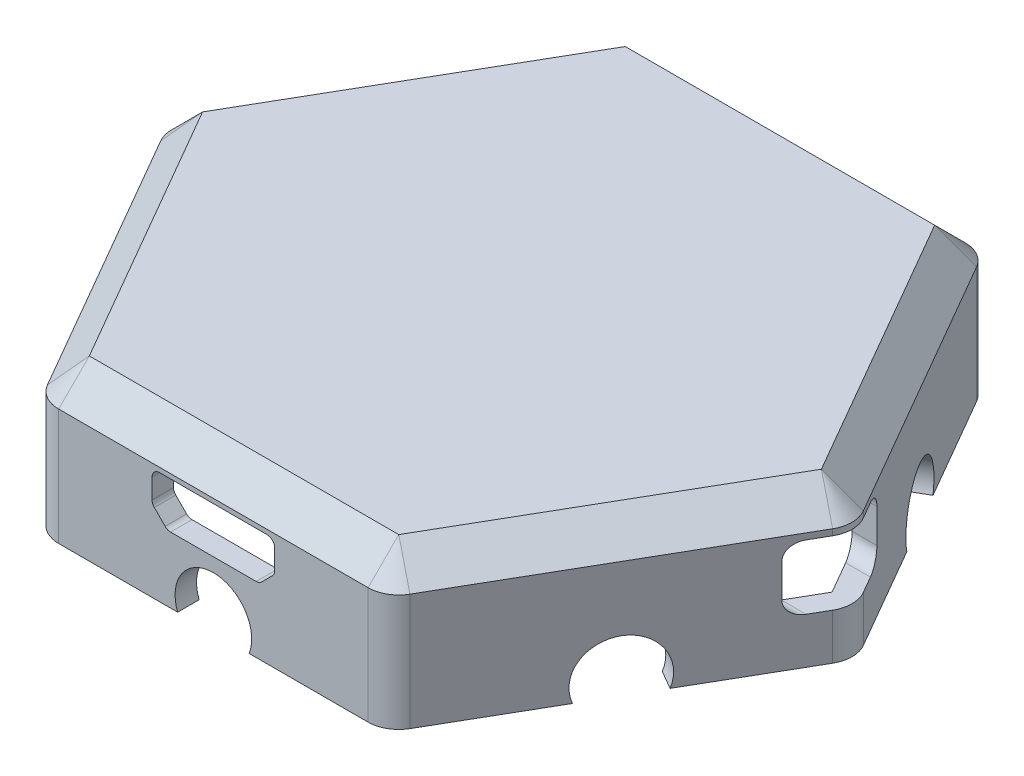
SolidWorks part; units mm, degrees
ref_plane "Front Plane" through (0, 0, 0) normal (0, 0, 1) x (1, 0, 0)
ref_plane "Top Plane" through (0, 0, 0) normal (0, 1, 0) x (1, 0, 0)
ref_plane "Right Plane" through (0, 0, 0) normal (1, 0, 0) x (0, 0, -1)
sketch "Sketch1" plane through (0, 0, 0) normal (0, 1, 0) x (1, 0, 0)
  line L0 (22.5, 0) -> (0, 0) construction
  line L1 (22.5, 0) -> (11.25, 19.4856)
  line L2 (11.25, 19.4856) -> (-11.25, 19.4856)
  line L3 (-11.25, 19.4856) -> (-22.5, 0)
  line L4 (-22.5, 0) -> (-11.25, -19.4856)
  line L5 (-11.25, -19.4856) -> (11.25, -19.4856)
  line L6 (11.25, -19.4856) -> (22.5, 0)
  circle A0 centre (0, 0) radius 19.4856 construction
  dimension "D1" = 22.5
extrude "Boss-Extrude1" add sketch "Sketch1" along normal blind 5
sketch "Sketch2" plane through (0, 0, 0) normal (0, -1, 0) x (1, 0, 0)
  line L0 (-10.4417, 18.0856) -> (-20.8834, 0)
  line L1 (-20.8834, 0) -> (-10.4417, -18.0856)
  line L2 (-10.4417, -18.0856) -> (10.4417, -18.0856)
  line L3 (10.4417, -18.0856) -> (20.8834, 0)
  line L4 (20.8834, 0) -> (10.4417, 18.0856)
  line L5 (10.4417, 18.0856) -> (-10.4417, 18.0856)
  line L6 (22.5, 0) -> (11.25, 19.4856)
  line L7 (11.25, 19.4856) -> (-11.25, 19.4856)
  line L8 (-11.25, 19.4856) -> (-22.5, 0)
  line L9 (-22.5, 0) -> (-11.25, -19.4856)
  line L10 (-11.25, -19.4856) -> (11.25, -19.4856)
  line L11 (11.25, -19.4856) -> (22.5, 0)
  line L12 (22.5, 0) -> (11.25, 19.4856)
  line L13 (11.25, 19.4856) -> (-11.25, 19.4856)
  line L14 (-11.25, 19.4856) -> (-22.5, 0)
  line L15 (-22.5, 0) -> (-11.25, -19.4856)
  line L16 (-11.25, -19.4856) -> (11.25, -19.4856)
  line L17 (11.25, -19.4856) -> (22.5, 0)
  dimension "D1" = 0
  dimension "D2" = 1.4
extrude "Cut-Extrude1" cut sketch "Sketch2" against normal blind 3.6 contours L4 L5 L0 L1 L2 L3 region at (0, 0, 0)
sketch "Sketch3" plane through (0, 0, 0) normal (0, -1, 0) x (1, 0, 0)
  line L6 (22.5, 0) -> (11.25, 19.4856)
  line L7 (11.25, 19.4856) -> (-11.25, 19.4856)
  line L8 (-11.25, 19.4856) -> (-22.5, 0)
  line L9 (-22.5, 0) -> (-11.25, -19.4856)
  line L10 (-11.25, -19.4856) -> (11.25, -19.4856)
  line L11 (11.25, -19.4856) -> (22.5, 0)
  line L12 (22.5, 0) -> (11.25, 19.4856)
  line L13 (11.25, 19.4856) -> (-11.25, 19.4856)
  line L14 (-11.25, 19.4856) -> (-22.5, 0)
  line L15 (-22.5, 0) -> (-11.25, -19.4856)
  line L16 (-11.25, -19.4856) -> (11.25, -19.4856)
  line L17 (11.25, -19.4856) -> (22.5, 0)
  line L18 (10.4417, 18.0856) -> (-10.4417, 18.0856)
  line L19 (20.8834, 0) -> (10.4417, 18.0856)
  line L20 (10.4417, -18.0856) -> (20.8834, 0)
  line L21 (-10.4417, -18.0856) -> (10.4417, -18.0856)
  line L22 (-20.8834, 0) -> (-10.4417, -18.0856)
  line L23 (-10.4417, 18.0856) -> (-20.8834, 0)
  line L24 (10.4417, 18.0856) -> (-10.4417, 18.0856)
  line L25 (20.8834, 0) -> (10.4417, 18.0856)
  line L26 (10.4417, -18.0856) -> (20.8834, 0)
  line L27 (-10.4417, -18.0856) -> (10.4417, -18.0856)
  line L28 (-20.8834, 0) -> (-10.4417, -18.0856)
  line L29 (-10.4417, 18.0856) -> (-20.8834, 0)
  dimension "D1" = 0
  dimension "D2" = 0
extrude "Boss-Extrude2" add sketch "Sketch3" along normal blind 4.6
fillet "Fillet1" radius 2 6 edges at (-11.25, 0.2, 19.4856) (-22.5, 0.2, 0) (-11.25, 0.2, -19.4856) (11.25, 0.2, -19.4856) (22.5, 0.2, 0) (11.25, 0.2, 19.4856)
sketch "Sketch4" plane through (0, 0, -19.4856) normal (0, 0, -1) x (-1, 0, 0)
  line L0 (0, -3.6) -> (0, -3.7) construction
  line L2 (0, -3.6) -> (0, 0) construction
  circle A0 centre (0, -3.7) radius 2.5
  dimension "D1" = 0.1
  dimension "D2" = 5
  dimension "D3" = 3.6
extrude "Cut-Extrude2" cut sketch "Sketch4" against normal up to next
ref_axis "Axis1" through (0, 4.51, 0) along (0, -1, 0)
pattern_circular "CirPattern1" count 6 every 60 about axis through (0, 4.51, 0) along (0, -1, 0) of "Cut-Extrude2"
sketch "Sketch5" plane through (0, 0, 19.4856) normal (0, 0, 1) x (1, 0, 0)
  line L3 (0, -0.3) -> (0, 2.7) construction
  line L4 (0, 5) -> (0, 2.7) construction
  line L5 (-10.0953, 5) -> (10.0953, 5) construction
  line L7 (-3.5, 2.7) -> (3.5, 2.7)
  line L8 (4, 2.2) -> (4, 0.9071)
  line L9 (3.8536, 0.5536) -> (3.1464, -0.1536)
  line L10 (2.7929, -0.3) -> (-2.7929, -0.3)
  line L11 (-3.8536, 0.5536) -> (-3.1464, -0.1536)
  line L12 (-4, 2.2) -> (-4, 0.9071)
  arc A4 (3.1464, -0.1536) -> (2.7929, -0.3) centre (2.7929, 0.2) cw
  arc A5 (4, 0.9071) -> (3.8536, 0.5536) centre (3.5, 0.9071) cw
  arc A6 (3.5, 2.7) -> (4, 2.2) centre (3.5, 2.2) cw
  arc A7 (-3.5, 2.7) -> (-4, 2.2) centre (-3.5, 2.2) ccw
  arc A8 (-4, 0.9071) -> (-3.8536, 0.5536) centre (-3.5, 0.9071) ccw
  arc A9 (-3.1464, -0.1536) -> (-2.7929, -0.3) centre (-2.7929, 0.2) ccw
  point P7 (3, -0.3)
  point P10 (4, 0.7)
  point P16 (4, 2.7)
  point P26 (-4, 2.7)
  point P27 (-4, 0.7)
  point P28 (-3, -0.3)
  dimension "D4" = 3
  dimension "D6" = 0.5
  dimension "D1" = 3
  dimension "D2" = 4
  dimension "D3" = 2
  dimension "D5" = 2.3
extrude "Cut-Extrude3" cut sketch "Sketch5" against normal blind 8
sketch "Sketch7" plane through (0, 0, 0) normal (1, 0, 0) x (0, 0, -1)
  line L0 (0, 0.5) -> (0, 5) construction
  line L1 (-3.1, -1.6) -> (3.1, -1.6)
  line L2 (-3.1, -1.6) -> (-3.1, 2.6)
  line L3 (-3.1, 2.6) -> (3.1, 2.6)
  line L4 (3.1, -1.6) -> (3.1, 2.6)
  line L5 (-3.1, -1.6) -> (3.1, 2.6) construction
  line L6 (-3.1, 2.6) -> (3.1, -1.6) construction
  line L7 (1, 5) -> (-1, 5) construction
  point P0 (0, 0.5)
  dimension "D1" = 4.2
  dimension "D2" = 6.2
  dimension "D3" = 4.5
extrude "Cut-Extrude4" cut sketch "Sketch7" against normal blind 10 from offset 22.5
fillet "Fillet2" radius 1 4 edges at (19.9019, -1.6, 3.1) (19.9019, -1.6, -3.1) (19.9019, 2.6, -3.1) (19.9019, 2.6, 3.1)
chamfer "Chamfer1" distance 2 angle 45 12 edges at (0, 5, 19.4856) (11.0953, 5, 19.2176) (-11.0953, 5, 19.2176) (16.875, 5, 9.7428) (-16.875, 5, 9.7428) (22.1906, 5, 0) (-22.1906, 5, 0) (16.875, 5, -9.7428) (-16.875, 5, -9.7428) (11.0953, 5, -19.2176) (-11.0953, 5, -19.2176) (0, 5, -19.4856)
chamfer "Chamfer2" distance 1 angle 45 6 edges at (15.6626, 3.6, 9.0428) (15.6626, 3.6, -9.0428) (0, 3.6, -18.0856) (0, 3.6, 18.0856) (-15.6626, 3.6, 9.0428) (-15.6626, 3.6, -9.0428)
sketch "Sketch12" plane through (0, 3.6, 0) normal (0, -1, 0) x (1, 0, 0)
  line L1 (-18.0412, -7.7229) -> (-16.8288, -7.0229) construction
  line L2 (-16.8288, -7.0229) -> (-20.8834, 0) construction
  line L3 (-20.8834, 0) -> (-16.8288, 7.0229) construction
  line L4 (-16.8288, 7.0229) -> (-18.0412, 7.7229) construction
  line L5 (-18.0412, 7.7229) -> (-21.9226, 1) construction
  line L6 (-21.9226, -1) -> (-18.0412, -7.7229) construction
  line L7 (-15.7088, 11.7627) -> (-14.4964, 11.0627)
  line L8 (-14.4964, 11.0627) -> (-10.4417, 18.0856)
  line L9 (-10.4417, 18.0856) -> (-2.3324, 18.0856)
  line L17 (19.7287, 0) -> (9.8644, 17.0856)
  line L18 (19.7287, 0) -> (9.8644, 17.0856)
  line L19 (9.8644, 17.0856) -> (-9.8644, 17.0856)
  line L30 (-2.3324, 18.0856) -> (-2.3324, 19.4856)
  line L31 (-2.3324, 19.4856) -> (-10.0953, 19.4856)
  line L32 (-11.8274, 18.4856) -> (-15.7088, 11.7627)
  line L33 (-15.7088, 11.7627) -> (-14.4964, 11.0627)
  line L34 (-14.4964, 11.0627) -> (-10.4417, 18.0856)
  line L35 (-10.4417, 18.0856) -> (-2.3324, 18.0856)
  line L36 (-2.3324, 18.0856) -> (-2.3324, 19.4856)
  line L37 (-2.3324, 19.4856) -> (-10.0953, 19.4856)
  line L38 (-11.8274, 18.4856) -> (-15.7088, 11.7627)
  line L39 (-14.4964, -11.0627) -> (-15.7088, -11.7627) construction
  line L40 (-15.7088, -11.7627) -> (-11.8274, -18.4856) construction
  line L41 (-10.0953, -19.4856) -> (-2.3324, -19.4856) construction
  line L42 (-2.3324, -19.4856) -> (-2.3324, -18.0856) construction
  line L43 (-2.3324, -18.0856) -> (-10.4417, -18.0856) construction
  line L44 (-10.4417, -18.0856) -> (-14.4964, -11.0627) construction
  line L45 (15.7088, -11.7627) -> (14.4964, -11.0627) construction
  line L46 (14.4964, -11.0627) -> (10.4417, -18.0856) construction
  line L47 (10.4417, -18.0856) -> (2.3324, -18.0856) construction
  line L48 (2.3324, -18.0856) -> (2.3324, -19.4856) construction
  line L49 (2.3324, -19.4856) -> (10.0953, -19.4856) construction
  line L50 (11.8274, -18.4856) -> (15.7088, -11.7627) construction
  line L51 (18.0412, 7.7229) -> (16.8288, 7.0229) construction
  line L52 (16.8288, 7.0229) -> (20.8834, 0) construction
  line L53 (20.8834, 0) -> (16.8288, -7.0229) construction
  line L54 (16.8288, -7.0229) -> (18.0412, -7.7229) construction
  line L55 (18.0412, -7.7229) -> (21.9226, -1) construction
  line L56 (21.9226, 1) -> (18.0412, 7.7229) construction
  line L57 (2.3324, 19.4856) -> (2.3324, 18.0856) construction
  line L58 (2.3324, 18.0856) -> (10.4417, 18.0856) construction
  line L59 (10.4417, 18.0856) -> (14.4964, 11.0627) construction
  line L60 (14.4964, 11.0627) -> (15.7088, 11.7627) construction
  line L61 (15.7088, 11.7627) -> (11.8274, 18.4856) construction
  line L62 (10.0953, 19.4856) -> (2.3324, 19.4856) construction
  line L63 (-18.0412, -7.7229) -> (-16.8288, -7.0229)
  line L64 (-16.8288, -7.0229) -> (-20.8834, 0)
  line L65 (-20.8834, 0) -> (-16.8288, 7.0229)
  line L66 (-16.8288, 7.0229) -> (-18.0412, 7.7229)
  line L67 (-18.0412, 7.7229) -> (-21.9226, 1)
  line L68 (-21.9226, -1) -> (-18.0412, -7.7229)
  line L69 (-14.4964, -11.0627) -> (-15.7088, -11.7627)
  line L70 (-15.7088, -11.7627) -> (-11.8274, -18.4856)
  line L71 (-10.0953, -19.4856) -> (-2.3324, -19.4856)
  line L72 (-2.3324, -19.4856) -> (-2.3324, -18.0856)
  line L73 (-2.3324, -18.0856) -> (-10.4417, -18.0856)
  line L74 (-10.4417, -18.0856) -> (-14.4964, -11.0627)
  line L75 (15.7088, -11.7627) -> (14.4964, -11.0627)
  line L76 (14.4964, -11.0627) -> (10.4417, -18.0856)
  line L77 (10.4417, -18.0856) -> (2.3324, -18.0856)
  line L78 (2.3324, -18.0856) -> (2.3324, -19.4856)
  line L79 (2.3324, -19.4856) -> (10.0953, -19.4856)
  line L80 (11.8274, -18.4856) -> (15.7088, -11.7627)
  line L81 (18.0412, 7.7229) -> (16.8288, 7.0229)
  line L82 (16.8288, 7.0229) -> (20.8834, 0)
  line L83 (20.8834, 0) -> (16.8288, -7.0229)
  line L84 (16.8288, -7.0229) -> (18.0412, -7.7229)
  line L85 (18.0412, -7.7229) -> (21.9226, -1)
  line L86 (21.9226, 1) -> (18.0412, 7.7229)
  line L87 (2.3324, 19.4856) -> (2.3324, 18.0856)
  line L88 (2.3324, 18.0856) -> (10.4417, 18.0856)
  line L89 (10.4417, 18.0856) -> (14.4964, 11.0627)
  line L90 (14.4964, 11.0627) -> (15.7088, 11.7627)
  line L91 (15.7088, 11.7627) -> (11.8274, 18.4856)
  line L92 (10.0953, 19.4856) -> (2.3324, 19.4856)
  line L105 (9.8644, 17.0856) -> (-9.8644, 17.0856)
  line L116 (-9.8644, 17.0856) -> (-19.7287, 0)
  line L117 (-9.8644, 17.0856) -> (-19.7287, 0)
  line L118 (-19.7287, 0) -> (-9.8644, -17.0856)
  line L119 (-19.7287, 0) -> (-9.8644, -17.0856)
  line L120 (-9.8644, -17.0856) -> (9.8644, -17.0856)
  line L121 (-9.8644, -17.0856) -> (9.8644, -17.0856)
  line L122 (9.8644, -17.0856) -> (19.7287, 0)
  line L123 (9.8644, -17.0856) -> (19.7287, 0)
  arc A0 (8.4417, 18.0856) -> (11.4417, 16.3535) centre (10.4417, 18.0856) ccw
  arc A1 (-21.9226, 1) -> (-21.9226, -1) centre (-20.1906, 0) ccw construction
  arc A2 (-10.0953, 19.4856) -> (-11.8274, 18.4856) centre (-10.0953, 17.4856) ccw
  arc A3 (-10.0953, 19.4856) -> (-11.8274, 18.4856) centre (-10.0953, 17.4856) ccw
  arc A4 (-11.8274, -18.4856) -> (-10.0953, -19.4856) centre (-10.0953, -17.4856) ccw construction
  arc A5 (10.0953, -19.4856) -> (11.8274, -18.4856) centre (10.0953, -17.4856) ccw construction
  arc A6 (21.9226, -1) -> (21.9226, 1) centre (20.1906, 0) ccw construction
  arc A7 (11.8274, 18.4856) -> (10.0953, 19.4856) centre (10.0953, 17.4856) ccw construction
  arc A8 (-21.9226, 1) -> (-21.9226, -1) centre (-20.1906, 0) ccw
  arc A9 (-11.8274, -18.4856) -> (-10.0953, -19.4856) centre (-10.0953, -17.4856) ccw
  arc A10 (10.0953, -19.4856) -> (11.8274, -18.4856) centre (10.0953, -17.4856) ccw
  arc A11 (21.9226, -1) -> (21.9226, 1) centre (20.1906, 0) ccw
  arc A12 (11.8274, 18.4856) -> (10.0953, 19.4856) centre (10.0953, 17.4856) ccw
  arc A13 (11.4417, -16.3535) -> (8.4417, -18.0856) centre (10.4417, -18.0856) ccw
  arc A14 (-8.4417, -18.0856) -> (-11.4417, -16.3535) centre (-10.4417, -18.0856) ccw
  arc A15 (-11.4417, 16.3535) -> (-8.4417, 18.0856) centre (-10.4417, 18.0856) ccw
  dimension "D2" = 0
  dimension "D3" = 2
  dimension "D4" = 2
  dimension "D1" = 0
extrude "Boss-Extrude3" add sketch "Sketch12" along normal blind 4.5 contours L105 A0 L18 | L117 A15 | A15 L35 L34 L117 | L18 A0 L89 L88 L105 | L76 A13 L123 L121 L77 | L123 A13 L121 | L73 A14 L121 L119 L74 | L121 A14 L119 region at (-9.9703, 3.6, 17.2691) region at (-9.614, 3.6, 16.652) region at (-9.614, 3.6, -16.652) region at (-9.9703, 3.6, -17.2691) region at (9.9703, 3.6, 17.2691) region at (9.614, 3.6, 16.652) region at (9.614, 3.6, -16.652) region at (9.9703, 3.6, -17.2691)
sketch "Sketch13" plane through (0, 3.6, 0) normal (0, -1, 0) x (1, 0, 0)
  line L0 (-8.6, -2.8165) -> (-5.3, -2.8165)
  line L1 (-5.3, -2.8165) -> (-5.3, -1.9265)
  line L2 (-5.3, -1.9265) -> (-8.6, -1.9265)
  line L3 (-8.6, -1.9265) -> (-8.6, -2.8165)
  line L4 (-8.6, -0.1066) -> (-5.3, -0.1066)
  line L5 (-5.3, -0.1066) -> (-5.3, 0.7835)
  line L6 (-5.3, 0.7835) -> (-8.6, 0.7835)
  line L7 (-8.6, 0.7835) -> (-8.6, -0.1066)
  line L8 (-8.6, 2.5835) -> (-5.3, 2.5835)
  line L9 (-5.3, 2.5835) -> (-5.3, 3.4735)
  line L10 (-5.3, 3.4735) -> (-8.6, 3.4735)
  line L11 (-8.6, 3.4735) -> (-8.6, 2.5835)
  line L12 (-10.7, -2.8165) -> (-9.8, -2.8165)
  line L13 (-9.8, -2.8165) -> (-9.8, 0.7835)
  line L14 (-9.8, 0.7835) -> (-10.7, 0.7835)
  line L15 (-10.7, 0.7835) -> (-10.7, -1.3165)
  line L16 (-14.5943, 3.4775) -> (-13.7, 3.4835)
  line L17 (-13.7, 1.9835) -> (-13.7, 0.7835)
  line L18 (-13.7, 0.7835) -> (-14.6, 0.7835)
  line L19 (-14.6, 0.7835) -> (-14.5943, 3.4775)
  line L20 (-10.7, -2.8165) -> (-13.7, 1.9835)
  line L21 (1.9, 0.7835) -> (1, 0.7835)
  line L22 (-13.7, 3.4835) -> (-10.7, -1.3165)
  line L24 (1.9, 0.7835) -> (1, 3.4835)
  line L25 (1, 3.4835) -> (0.1, 3.4835)
  line L26 (0.1, 3.4835) -> (1, 0.7835)
  line L27 (4.3, 0.7835) -> (5.2, 3.4835)
  line L28 (5.2, 3.4835) -> (4.3, 3.4835)
  line L29 (4.3, 3.4835) -> (3.4, 0.7835)
  line L30 (11.5, 0.7835) -> (11.5, 3.4835)
  line L31 (11.5, 3.4835) -> (10.6, 3.4835)
  line L32 (10.6, 3.4835) -> (10.6, 0.7835)
  line L33 (10.6, 0.7835) -> (11.5, 0.7835)
  line L34 (8.8, -2.8165) -> (9.7, -2.8165)
  line L35 (9.7, -2.8165) -> (8.5, 0.7835)
  line L36 (8.5, 0.7835) -> (7.6, 0.7835)
  line L37 (6.7, 0.7835) -> (5.8, 0.7835)
  line L38 (5.8, 0.7835) -> (4.6, -2.8165)
  line L39 (4.6, -2.8165) -> (5.5, -2.8165)
  line L40 (-2.6, 0.7835) -> (-2.9, 0.7835)
  line L41 (-2.9, 0.7835) -> (-3.2, 0.7835)
  line L42 (-3.2, 0.7835) -> (-4.1, 0.7835)
  line L43 (-4.1, 0.7835) -> (-4.0789, -2.8165)
  line L44 (-4.0789, -2.8165) -> (-3.2, -2.8165)
  line L45 (-3.2, -2.8165) -> (-3.2, -0.1165)
  line L46 (-3.2, -0.1165) -> (-2.9, -0.1165)
  line L47 (-0.8, -2.8165) -> (0.1, -2.8165)
  line L48 (-1.428, 0.2126) -> (-1.428, 0.2403)
  line L49 (-4.1, 3.4835) -> (-4.1, 2.5835)
  line L81 (10.6, -2.8165) -> (13.9, -2.8165)
  line L82 (13.9, -2.8165) -> (13.9, -1.9265)
  line L83 (13.9, -1.9265) -> (10.6, -1.9265)
  line L84 (10.6, -1.9265) -> (10.6, -2.8165)
  line L88 (-2.6, 2.5835) -> (-4.1, 2.5835)
  line L89 (4.3, 0.7835) -> (3.4, 0.7835)
  line L90 (8.8, -2.8165) -> (7.6, 0.7835)
  line L91 (6.7, 0.7835) -> (5.5, -2.8165)
  spline S0 degree 3 poles (-2.6, 2.5835) (-1.85, 2.5835) (-1.1, 2.4335) (-1.1, 1.6835) knots 0 0 0 0 1 1 1 1
  spline S1 degree 3 poles (-1.1, 1.6835) (-1.1, 0.9335) (-1.7, 0.7835) (-2.6, 0.7835) knots 1 1 1 1 2 2 2 2
  spline S2 degree 3 poles (-2.9, -0.1165) (-2.1722, -0.1165) (-1.4704, -0.4546) (-1.286, -1.313) knots 9 9 9 9 10 10 10 10
  spline S3 degree 3 poles (-1.286, -1.313) (-1.111, -2.0882) (-0.9015, -2.5212) (-0.8, -2.8165) knots 10 10 10 10 11 11 11 11
  spline S4 degree 3 poles (0.1, -2.8165) (-0.0292, -2.5212) (-0.3731, -1.9874) (-0.5697, -1.1185) knots 12 12 12 12 13 13 13 13
  spline S5 degree 3 poles (-0.5697, -1.1185) (-0.598, -0.9934) (-0.8, 0.0335) (-1.428, 0.2126) knots 13 13 13 13 14 14 14 14
  spline S6 degree 3 poles (-1.428, 0.2403) (-0.5, 0.3335) (-0.2, 1.2335) (-0.2, 1.6835) knots 15 15 15 15 16 16 16 16
  spline S7 degree 3 poles (-0.2, 1.6835) (-0.2, 2.1335) (-0.5, 2.7335) (-0.7758, 2.9201) knots 16 16 16 16 17 17 17 17
  spline S8 degree 3 poles (-0.7758, 2.9201) (-0.9479, 3.0366) (-1.4, 3.4835) (-2.6, 3.4835) knots 17 17 17 17 18 18 18 18
  spline S9 degree 3 poles (-2.6, 3.4835) (-3.1528, 3.4835) (-3.6369, 3.4835) (-4.1, 3.4835) knots 18 18 18 18 19 19 19 19
extrude "Cut-Extrude7" cut sketch "Sketch13" against normal offset from surface (0.9 mm away) 0.5 up to face at (0, 5, 0)
sketch "Sketch14" plane through (0, 4.5, 0) normal (0, -1, 0) x (1, 0, 0)
  line L0 (7.6, 0.7835) -> (8.8, -2.8165) construction
  line L1 (8.8, -2.8165) -> (9.7, -2.8165) construction
  line L2 (9.7, -2.8165) -> (8.5, 0.7835) construction
  line L3 (8.5, 0.7835) -> (7.6, 0.7835) construction
  line L4 (-8.6, -1.9265) -> (-8.6, -2.8165)
  line L5 (-8.6, -2.8165) -> (-5.3, -2.8165)
  line L6 (-5.3, -2.8165) -> (-5.3, -1.9265)
  line L7 (-5.3, -1.9265) -> (-8.6, -1.9265)
  line L8 (-8.6, -1.9265) -> (-8.6, -2.8165)
  line L9 (-8.6, -2.8165) -> (-5.3, -2.8165)
  line L10 (-5.3, -2.8165) -> (-5.3, -1.9265)
  line L11 (-5.3, -1.9265) -> (-8.6, -1.9265)
  line L12 (5.5, -2.8165) -> (6.7, 0.7835) construction
  line L13 (6.7, 0.7835) -> (5.8, 0.7835) construction
  line L14 (5.8, 0.7835) -> (4.6, -2.8165) construction
  line L15 (4.6, -2.8165) -> (5.5, -2.8165) construction
  line L16 (-8.6, 3.4735) -> (-8.6, 2.5835) construction
  line L17 (-8.6, 2.5835) -> (-5.3, 2.5835) construction
  line L18 (-5.3, 2.5835) -> (-5.3, 3.4735) construction
  line L19 (-5.3, 3.4735) -> (-8.6, 3.4735) construction
  line L20 (-8.6, 0.7835) -> (-8.6, -0.1066) construction
  line L21 (-8.6, -0.1066) -> (-5.3, -0.1066) construction
  line L22 (-5.3, -0.1066) -> (-5.3, 0.7835) construction
  line L23 (-5.3, 0.7835) -> (-8.6, 0.7835) construction
  line L24 (7.6, 0.7835) -> (8.8, -2.8165)
  line L25 (8.8, -2.8165) -> (9.7, -2.8165)
  line L26 (9.7, -2.8165) -> (8.5, 0.7835)
  line L27 (8.5, 0.7835) -> (7.6, 0.7835)
  line L28 (5.5, -2.8165) -> (6.7, 0.7835)
  line L29 (6.7, 0.7835) -> (5.8, 0.7835)
  line L30 (5.8, 0.7835) -> (4.6, -2.8165)
  line L31 (4.6, -2.8165) -> (5.5, -2.8165)
  line L32 (-8.6, 3.4735) -> (-8.6, 2.5835)
  line L33 (-8.6, 2.5835) -> (-5.3, 2.5835)
  line L34 (-5.3, 2.5835) -> (-5.3, 3.4735)
  line L35 (-5.3, 3.4735) -> (-8.6, 3.4735)
  line L36 (-8.6, 0.7835) -> (-8.6, -0.1066)
  line L37 (-8.6, -0.1066) -> (-5.3, -0.1066)
  line L38 (-5.3, -0.1066) -> (-5.3, 0.7835)
  line L39 (-5.3, 0.7835) -> (-8.6, 0.7835)
  dimension "D1" = 0
extrude "Cut-Extrude8" cut sketch "Sketch14" against normal blind 0.1
sketch "Sketch15" plane through (0, 4.5, 0) normal (0, -1, 0) x (1, 0, 0)
  line L0 (10.6, -1.9265) -> (10.6, -2.8165) construction
  line L1 (10.6, -2.8165) -> (13.9, -2.8165) construction
  line L2 (13.9, -2.8165) -> (13.9, -1.9265) construction
  line L3 (13.9, -1.9265) -> (10.6, -1.9265) construction
  line L4 (10.6, 0.7835) -> (11.5, 0.7835) construction
  line L5 (11.5, 0.7835) -> (11.5, 3.4835) construction
  line L6 (11.5, 3.4835) -> (10.6, 3.4835) construction
  line L7 (10.6, 3.4835) -> (10.6, 0.7835) construction
  line L8 (-13.7, 1.9835) -> (-10.7, -2.8165) construction
  line L9 (-10.7, -2.8165) -> (-9.8, -2.8165) construction
  line L10 (-9.8, -2.8165) -> (-9.8, 0.7835) construction
  line L11 (-9.8, 0.7835) -> (-10.7, 0.7835) construction
  line L12 (-10.7, 0.7835) -> (-10.7, -1.3165) construction
  line L13 (-10.7, -1.3165) -> (-13.7, 3.4835) construction
  line L14 (-13.7, 3.4835) -> (-14.5943, 3.4775) construction
  line L15 (-14.5943, 3.4775) -> (-14.6, 0.7835) construction
  line L16 (-14.6, 0.7835) -> (-13.7, 0.7835) construction
  line L17 (-13.7, 0.7835) -> (-13.7, 1.9835) construction
  line L18 (10.6, -1.9265) -> (10.6, -2.8165)
  line L19 (10.6, -2.8165) -> (13.9, -2.8165)
  line L20 (13.9, -2.8165) -> (13.9, -1.9265)
  line L21 (13.9, -1.9265) -> (10.6, -1.9265)
  line L22 (10.6, 0.7835) -> (11.5, 0.7835)
  line L23 (11.5, 0.7835) -> (11.5, 3.4835)
  line L24 (11.5, 3.4835) -> (10.6, 3.4835)
  line L25 (10.6, 3.4835) -> (10.6, 0.7835)
  line L26 (-13.7, 1.9835) -> (-10.7, -2.8165)
  line L27 (-10.7, -2.8165) -> (-9.8, -2.8165)
  line L28 (-9.8, -2.8165) -> (-9.8, 0.7835)
  line L29 (-9.8, 0.7835) -> (-10.7, 0.7835)
  line L30 (-10.7, 0.7835) -> (-10.7, -1.3165)
  line L31 (-10.7, -1.3165) -> (-13.7, 3.4835)
  line L32 (-13.7, 3.4835) -> (-14.5943, 3.4775)
  line L33 (-14.5943, 3.4775) -> (-14.6, 0.7835)
  line L34 (-14.6, 0.7835) -> (-13.7, 0.7835)
  line L35 (-13.7, 0.7835) -> (-13.7, 1.9835)
extrude "Cut-Extrude9" cut sketch "Sketch15" against normal blind 0.2
